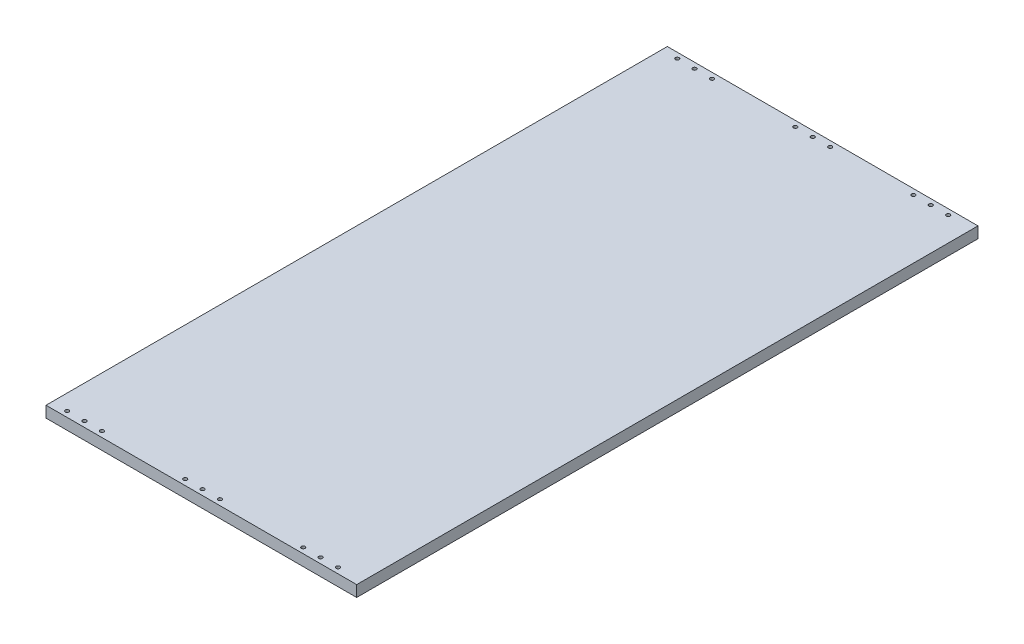
SolidWorks part; units mm, degrees
ref_plane "Спереди" through (0, 0, 0) normal (0, 0, 1) x (1, 0, 0)
ref_plane "Сверху" through (0, 0, 0) normal (0, 1, 0) x (1, 0, 0)
ref_plane "Справа" through (0, 0, 0) normal (1, 0, 0) x (0, 0, -1)
sketch "Эскиз2" plane through (0, 0, 0) normal (0, 1, 0) x (1, 0, 0)
  line L1 (0, 0) -> (500, 0)
  line L2 (0, 0) -> (0, 1000)
  line L3 (0, 1000) -> (500, 1000)
  line L4 (500, 0) -> (500, 1000)
extrude "Бобышка-Вытянуть1" add sketch "Эскиз2" along normal blind 18
sketch "Эскиз3" plane through (0, 18, 0) normal (0, 1, 0) x (1, 0, 0)
  line L0 (0, 500) -> (537.494, 500) construction
  line L1 (0, 1000) -> (0, 0) construction
  circle A0 centre (25, 9) radius 3
  circle A1 centre (53, 9) radius 3
  circle A2 centre (81, 9) radius 3
  circle A3 centre (215, 9) radius 3
  circle A4 centre (243, 9) radius 3
  circle A5 centre (271, 9) radius 3
  circle A6 centre (405, 9) radius 3
  circle A7 centre (433, 9) radius 3
  circle A8 centre (461, 9) radius 3
  circle A9 centre (461, 991) radius 3
  circle A10 centre (433, 991) radius 3
  circle A11 centre (405, 991) radius 3
  circle A12 centre (271, 991) radius 3
  circle A13 centre (243, 991) radius 3
  circle A14 centre (215, 991) radius 3
  circle A15 centre (81, 991) radius 3
  circle A16 centre (53, 991) radius 3
  circle A17 centre (25, 991) radius 3
  dimension "D1" = 3
  dimension "D2" = 3
extrude "Вырез-Вытянуть1" cut sketch "Эскиз3" against normal blind 9
